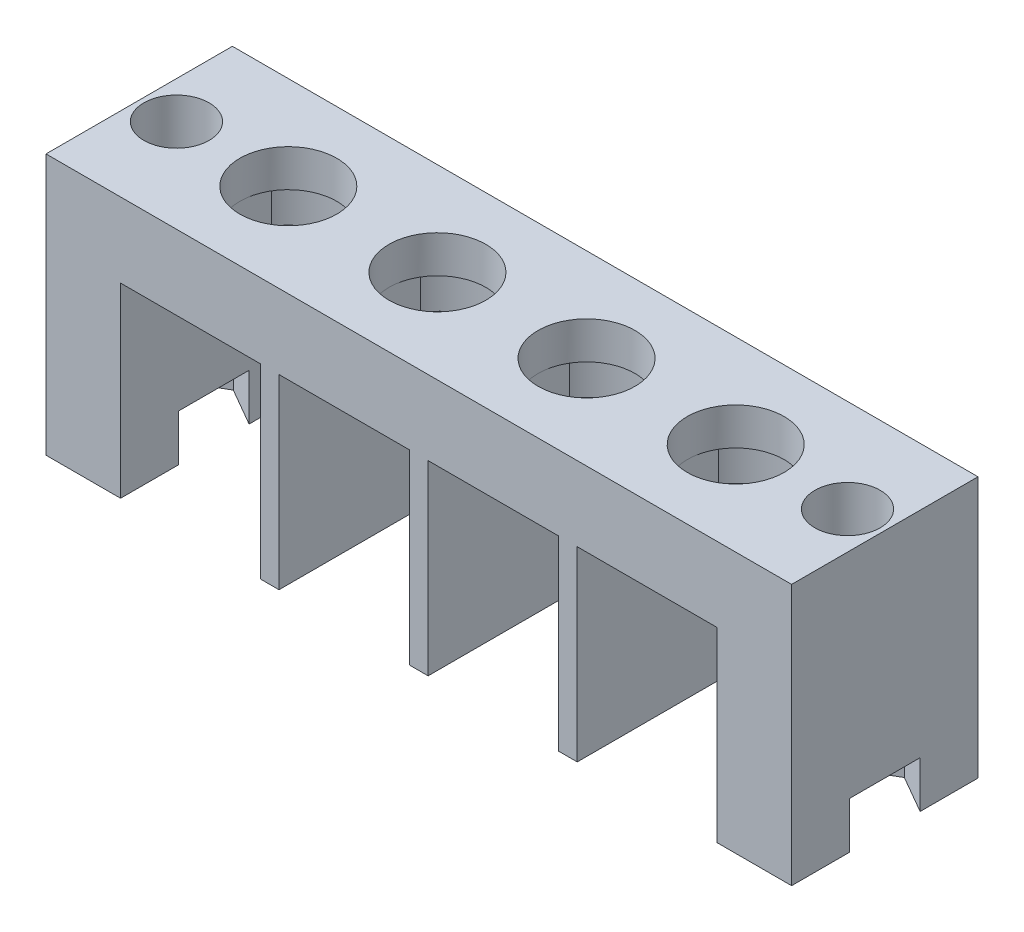
SolidWorks part; units mm, degrees
ref_plane "Płaszczyzna przednia" through (0, 0, 0) normal (0, 0, 1) x (1, 0, 0)
ref_plane "Płaszczyzna górna" through (0, 0, 0) normal (0, 1, 0) x (1, 0, 0)
ref_plane "Płaszczyzna prawa" through (0, 0, 0) normal (1, 0, 0) x (0, 0, -1)
sketch "Sketch1" plane through (0, 0, 0) normal (0, 1, 0) x (1, 0, 0)
  line L1 (-25, -7.3826) -> (15, -7.3826)
  line L2 (-25, -7.3826) -> (-25, 2.6174)
  line L3 (-25, 2.6174) -> (15, 2.6174)
  line L4 (15, -7.3826) -> (15, 2.6174)
  dimension "D1" = 40
  dimension "D2" = 10
extrude "Boss-Extrude1" add sketch "Sketch1" along normal blind 4
sketch "Sketch2" plane through (0, 4, 0) normal (0, 1, 0) x (1, 0, 0)
  line L0 (-25, -2.3826) -> (15, -2.3826) construction
  line L1 (-25, 2.6174) -> (-25, -7.3826) construction
  line L2 (15, -7.3826) -> (15, 2.6174) construction
  line L3 (15, -2.3826) -> (7, -2.3826) construction
  line L4 (7, -2.3826) -> (-1, -2.3826) construction
  line L5 (-1, -2.3826) -> (-9, -2.3826) construction
  line L6 (-9, -2.3826) -> (-17, -2.3826) construction
  circle A0 centre (-17, -2.3826) radius 2.6
  circle A1 centre (-9, -2.3826) radius 2.6
  circle A2 centre (-1, -2.3826) radius 2.6
  circle A3 centre (7, -2.3826) radius 2.6
  dimension "D5" = 8
  dimension "D1" = 8
  dimension "D2" = 8
  dimension "D3" = 8
  dimension "D4" = 8
extrude "Cut-Extrude1" cut sketch "Sketch2" against normal blind 10
sketch "Sketch3" plane through (0, 0, 0) normal (0, -1, 0) x (1, 0, 0)
  line L0 (-19.6, 4.0707) -> (-19.6, 0.6944)
  line L2 (-11.6, 4.0707) -> (-11.6, 0.6944)
  line L4 (-3.6, 4.0707) -> (-3.6, 0.6944)
  line L6 (4.4, 4.0707) -> (4.4, 0.6944)
  arc A0 (-19.6, 0.6944) -> (-19.6, 4.0707) centre (-17, 2.3826) ccw
  arc A1 (-11.6, 0.6944) -> (-11.6, 4.0707) centre (-9, 2.3826) ccw
  arc A2 (-3.6, 0.6944) -> (-3.6, 4.0707) centre (-1, 2.3826) ccw
  arc A3 (4.4, 0.6944) -> (4.4, 4.0707) centre (7, 2.3826) ccw
extrude "Cut-Extrude4" cut sketch "Sketch3" against normal blind 2
sketch "Sketch5" plane through (0, 0, 0) normal (0, -1, 0) x (1, 0, 0)
  line L0 (15, 7.3826) -> (15, -2.6174) construction
  line L5 (-25, -2.6174) -> (15, -2.6174)
  line L10 (-25, -2.6174) -> (-25, -1.6174)
  line L17 (-21, -1.6174) -> (-13.5, -1.6174)
  line L50 (15, -2.6174) -> (15, -1.6174)
  line L59 (-25, 2.8826) -> (-13.5, 2.8826) construction
  line L60 (-25, 7.3826) -> (-21, 7.3826)
  line L61 (-25, 7.3826) -> (-25, -1.6174)
  line L63 (-21, 7.3826) -> (-21, -1.6174)
  line L64 (15, 7.3826) -> (11, 7.3826)
  line L65 (15, 7.3826) -> (15, -1.6174)
  line L67 (11, 7.3826) -> (11, -1.6174)
  line L68 (-13.5, 2.8826) -> (-13.5, 7.3826) construction
  line L69 (-25, 7.3826) -> (15, 7.3826) construction
  line L70 (-13.5, 7.3826) -> (-13.5, -1.6174) construction
  line L71 (-13.5, 2.8826) -> (-5.5, 2.8826) construction
  line L72 (-5.5, 2.8826) -> (-5.5, 7.3826) construction
  line L73 (-5.5, 7.3826) -> (-5.5, -1.6174) construction
  line L74 (-5.5, 2.8826) -> (2.5, 2.8826) construction
  line L75 (2.5, 2.8826) -> (2.5, 7.3826) construction
  line L76 (2.5, 7.3826) -> (2.5, -1.6174) construction
  line L77 (-12.5, -1.6174) -> (-5.5, -1.6174)
  line L79 (-13.5, -1.6174) -> (-13.5, 7.3826)
  line L80 (-13.5, 7.3826) -> (-12.5, 7.3826)
  line L81 (-12.5, -1.6174) -> (-12.5, 7.3826)
  line L83 (-5.5, -1.6174) -> (-5.5, 7.3826)
  line L84 (-5.5, 7.3826) -> (-4.5, 7.3826)
  line L85 (-4.5, -1.6174) -> (-4.5, 7.3826)
  line L87 (2.5, -1.6174) -> (2.5, 7.3826)
  line L88 (2.5, 7.3826) -> (3.5, 7.3826)
  line L89 (3.5, -1.6174) -> (3.5, 7.3826)
  line L90 (-4.5, -1.6174) -> (2.5, -1.6174)
  line L91 (3.5, -1.6174) -> (11, -1.6174)
  line M18 (15, 7.3826) -> (-25, 7.3826)
  line M23 (-25, 7.3826) -> (-25, -2.6174)
  line M24 (-25, -2.6174) -> (15, -2.6174)
  line M25 (15, -2.6174) -> (15, 7.3826)
  dimension "D1" = 1
  dimension "D2" = 4
  dimension "D3" = 4
  dimension "D4" = 1
  dimension "D5" = 1
  dimension "D6" = 1
extrude "Boss-Extrude4" add sketch "Sketch5" along normal blind 10 contours L90 L85 M18 M23 M24 M25 region at (-5, 0, 1.4437)
sketch "Sketch6" plane through (0, -10, 0) normal (0, -1, 0) x (1, 0, 0)
  line L0 (-23, 7.3826) -> (-23, -2.6174) construction
  line L1 (-21, 7.3826) -> (-25, 7.3826) construction
  line L2 (-25, -2.6174) -> (15, -2.6174) construction
  line L3 (-23, -2.6174) -> (-23, 2.3826) construction
  line L4 (-23, 2.3826) -> (-25, 2.3826) construction
  line L5 (-25, 7.3826) -> (-25, -2.6174) construction
  line L6 (13, 7.3826) -> (13, -2.6174) construction
  line L7 (15, 7.3826) -> (11, 7.3826) construction
  circle A0 centre (-23, 2.3826) radius 1.75
  circle A1 centre (13, 2.3826) radius 1.75
extrude "Cut-Extrude5" cut sketch "Sketch6" against normal blind 40
sketch "Sketch8" plane through (0, -10, 0) normal (0, -1, 0) x (1, 0, 0)
  line L1 (13, 5.4326) -> (10.3586, 3.9076)
  line L2 (10.3586, 3.9076) -> (10.3586, 0.8576)
  line L3 (10.3586, 0.8576) -> (13, -0.6674)
  line L4 (13, -0.6674) -> (15.6414, 0.8576)
  line L5 (15.6414, 0.8576) -> (15.6414, 3.9076)
  line L6 (15.6414, 3.9076) -> (13, 5.4326)
  line L7 (-23, 5.4326) -> (-25.6414, 3.9076)
  line L8 (-25.6414, 3.9076) -> (-25.6414, 0.8576)
  line L9 (-25.6414, 0.8576) -> (-23, -0.6674)
  line L10 (-23, -0.6674) -> (-20.3586, 0.8576)
  line L11 (-20.3586, 0.8576) -> (-20.3586, 3.9076)
  line L12 (-20.3586, 3.9076) -> (-23, 5.4326)
  circle A0 centre (13, 2.3826) radius 3.05 construction
  circle A1 centre (-23, 2.3826) radius 2.6414 construction
extrude "Cut-Extrude6" cut sketch "Sketch8" against normal blind 2.5
